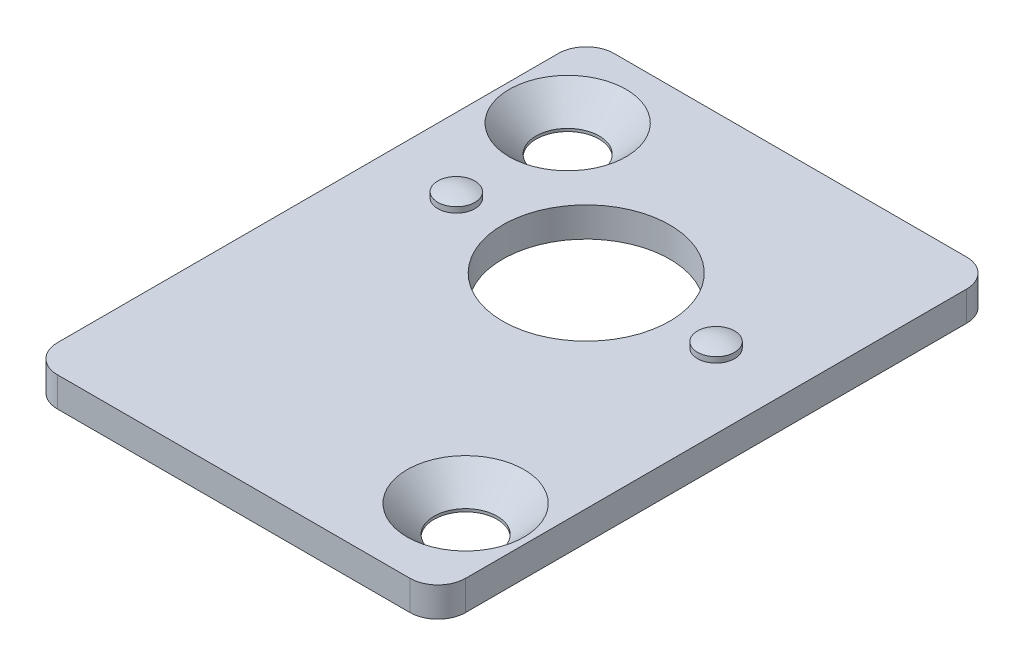
SolidWorks part; units mm, degrees
material "Chrome Stainless Steel"
ref_plane "Front Plane" through (0, 0, 0) normal (0, 0, 1) x (1, 0, 0)
ref_plane "Top Plane" through (0, 0, 0) normal (0, 1, 0) x (1, 0, 0)
ref_plane "Right Plane" through (0, 0, 0) normal (1, 0, 0) x (0, 0, -1)
sketch "BaseS" plane through (0, 0, 0) normal (0, 1, 0) x (1, 0, 0)
  line L1 (-11, 15) -> (11, 15)
  line L2 (-11, 15) -> (-11, -15)
  line L3 (-11, -15) -> (11, -15)
  line L4 (11, 15) -> (11, -15)
  line L5 (-11, 15) -> (11, -15) construction
  line L6 (-11, -15) -> (11, 15) construction
  point P0 (0, 0)
  dimension "D1" = 22
  dimension "D2" = 30
extrude "BASE" add sketch "BaseS" against normal blind 1.6
hole_wizard "CSK for M3 Flat Head Machine Screw1" positions "Sketch2" profile "Sketch3" countersink size "M3" standard "ANSI Metric"
sketch "Sketch2" plane through (0, 0, 0) normal (0, 1, 0) x (1, 0, 0)
  line L0 (-11, 15) -> (-11, -15) construction
  line L1 (11, -15) -> (11, 15) construction
  line L2 (11, 15) -> (-11, 15) construction
  line L3 (-11, -15) -> (11, -15) construction
  point P0 (-7.5, 10.5)
  point P2 (7.5, -10)
  dimension "D1" = 3.5
  dimension "D2" = 3.5
  dimension "D3" = 4.5
  dimension "D4" = 5
  dimension "D5" = 20.5
  dimension "D6" = 15
sketch "Sketch3" plane through (-7.5, 0, -10.5) normal (1, 0, 0) x (0, 0, 1)
  line L0 (0, 0) -> (0, 12.0215)
  line L1 (0, 12.0215) -> (1.7, 11)
  line L2 (1.7, 11) -> (1.7, 1.45)
  line L3 (1.7, 1.45) -> (3.15, 0)
  line L5 (3.15, 0) -> (0, 0)
  line L6 (-1.7, 1.45) -> (-3.15, 0) construction
  line L10 (0, 12.0215) -> (-1.7, 11) construction
  line L11 (0, -6.35) -> (0, 107.95) construction
  dimension "Hole Dia." = 3.4
  dimension "Hole Depth" = 11
  dimension "Near C'Sink Dia." = 6.3
  dimension "Near C'Sink Angle" = 90
  dimension "Drill Angle" = 118
sketch "BoreS" plane through (0, 0, 0) normal (0, 1, 0) x (1, 0, 0)
  line L0 (0, 15) -> (0, 4) construction
  line L1 (11, 15) -> (-11, 15) construction
  circle A0 centre (0, 4) radius 4.5
  dimension "D1" = 9
  dimension "D2" = 11
extrude "BORE" cut sketch "BoreS" against normal through all
sketch "LockingFeatureS" plane through (0, 0, 0) normal (0, 1, 0) x (1, 0, 0)
  line L0 (0, 4) -> (-7, 4) construction
  circle A0 centre (-7, 4) radius 1
  circle A1 centre (0, 4) radius 4.5 construction
  dimension "D1" = 2
  dimension "D2" = 7
extrude "LOCKING FEATURE" add sketch "LockingFeatureS" along normal blind 0.3
dome "LF DOME" faces to dome 1 distance 0.2 reverse direction no elliptical dome no face at (-7, 0.3, -3) parameters "D1"=0.2
mirror "LF HM" about plane through (0, 0, 0) normal (1, 0, 0) of "LF DOME", "LOCKING FEATURE"
sketch "LFBottomCut" plane through (0, -1.6, 0) normal (0, -1, 0) x (-1, 0, 0)
  circle A0 centre (7, 4) radius 1
  circle A1 centre (-7, 4) radius 1
  circle A2 centre (7, 4) radius 1 construction
extrude "LF BOTTOM CUT" cut sketch "LFBottomCut" against normal blind 0.3
fillet "BASE FILLET" radius 1.5 4 edges at (-11, -0.8, -15) (11, -0.8, -15) (11, -0.8, 15) (-11, -0.8, 15)
